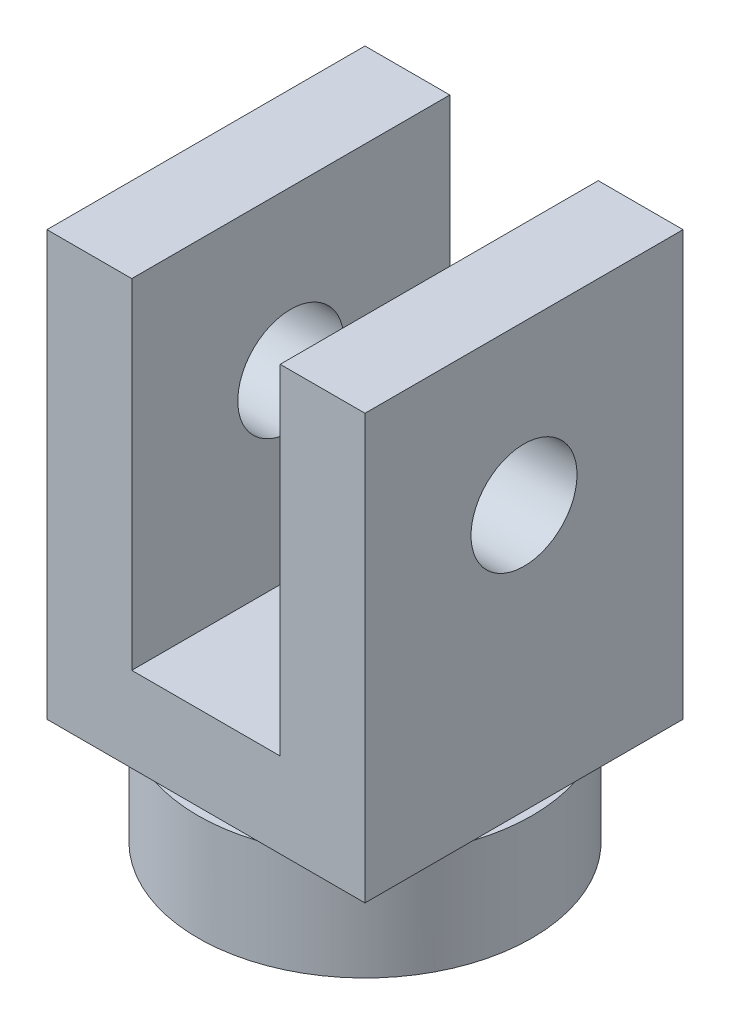
SolidWorks part; units mm, degrees
ref_plane "Front Plane" through (0, 0, 0) normal (0, 0, 1) x (1, 0, 0)
ref_plane "Top Plane" through (0, 0, 0) normal (0, 1, 0) x (1, 0, 0)
ref_plane "Right Plane" through (0, 0, 0) normal (1, 0, 0) x (0, 0, -1)
sketch "Sketch1" plane through (0, 0, 0) normal (0, 0, 1) x (1, 0, 0)
  line L0 (0, -1000) -> (0, 49000) construction
  line L1 (-1000, 0) -> (49000, 0) construction
  line L2 (-9.525, 12.7) -> (-9.525, -12.7)
  line L3 (-9.525, -12.7) -> (9.525, -12.7)
  line L4 (9.525, -12.7) -> (9.525, 12.7)
  line L5 (-4.445, 12.7) -> (-4.445, -7.62)
  line L6 (-4.445, -7.62) -> (4.445, -7.62)
  line L7 (4.445, -7.62) -> (4.445, 12.7)
  line L8 (-9.525, 12.7) -> (-4.445, 12.7)
  line L9 (4.445, 12.7) -> (9.525, 12.7)
  line L10 (-4.445, 12.7) -> (-4.445, -7.62) construction
  line L11 (-4.445, -7.62) -> (4.445, -7.62) construction
  line L12 (4.445, -7.62) -> (4.445, 12.7) construction
  dimension "D1" = 25.4
  dimension "D2" = 19.05
  dimension "D4" = 5.08
  dimension "D3" = 5.08
extrude "Boss-Extrude1" add sketch "Sketch1" along normal mid plane 19.05
sketch "Sketch2" plane through (0, -12.7, 0) normal (0, -1, 0) x (1, 0, 0)
  circle A0 centre (0, 0) radius 10
  dimension "D1" = 20
extrude "Boss-Extrude2" add sketch "Sketch2" along normal blind 6.35
sketch "Sketch3" plane through (0, -19.05, 0) normal (0, -1, 0) x (1, 0, 0)
  circle A0 centre (0, 0) radius 3.175
  dimension "D1" = 6.35
extrude "Cut-Extrude1" cut sketch "Sketch3" against normal up to next
sketch "Sketch4" plane through (9.525, 0, 0) normal (1, 0, 0) x (0, 0, -1)
  line L0 (0, -1000) -> (0, 49000) construction
  line L1 (0, 6.35) -> (-22.9794, 6.35) construction
  line L2 (-9.525, 12.7) -> (9.525, 12.7) construction
  circle A0 centre (0, 3.175) radius 3.175
  dimension "D1" = 6.35
  dimension "D2" = 6.35
extrude "Cut-Extrude2" cut sketch "Sketch4" against normal through all
ref_plane "Plane1" through (10.525, 0, 0) normal (1, 0, 0) x (0, 0, -1)
ref_axis "Axis1" through (0, -7.62, 0) along (0, -1, 0)
